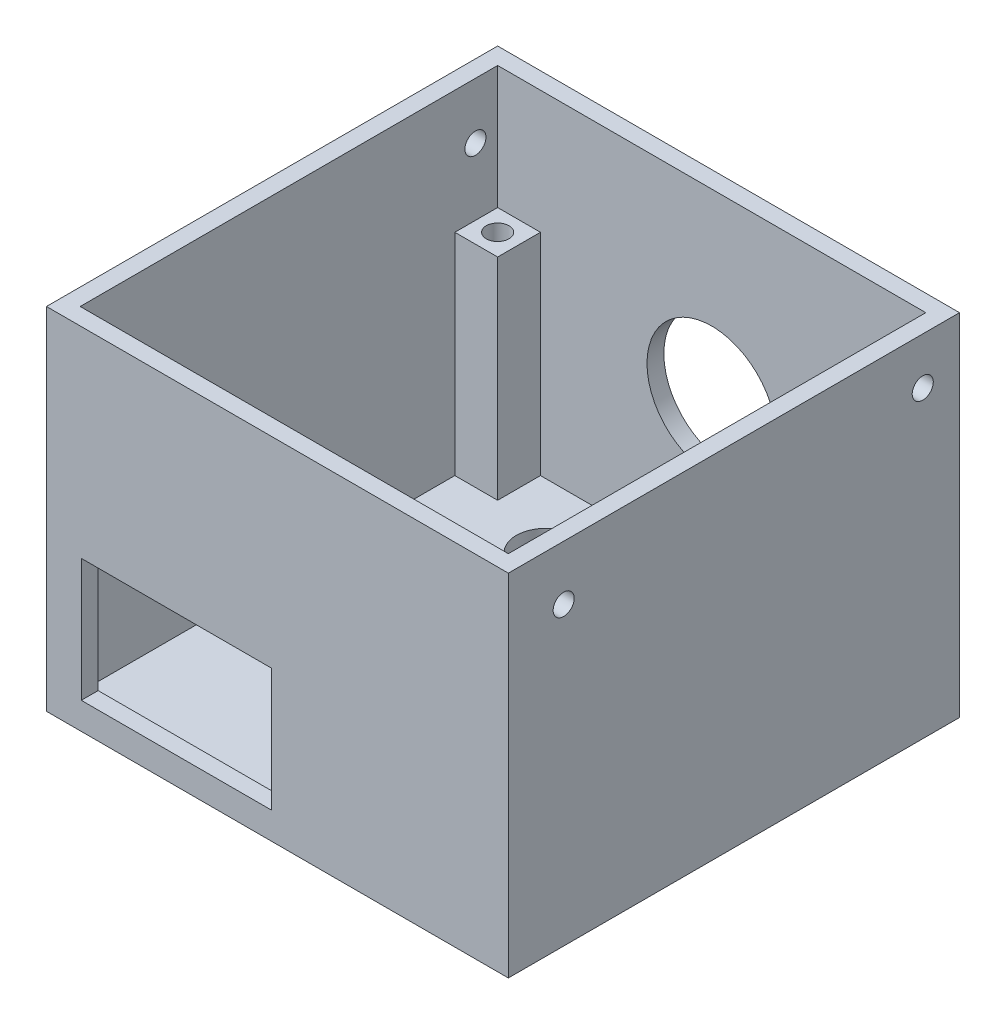
SolidWorks part; units mm, degrees
ref_plane "Front Plane" through (0, 0, 0) normal (0, 0, 1) x (1, 0, 0)
ref_plane "Top Plane" through (0, 0, 0) normal (0, 1, 0) x (1, 0, 0)
ref_plane "Right Plane" through (0, 0, 0) normal (1, 0, 0) x (0, 0, -1)
sketch "Sketch1" plane through (0, 0, 0) normal (0, 1, 0) x (1, 0, 0)
  line L1 (27.4, -26.765) -> (-27.4, -26.765)
  line L2 (27.4, -26.765) -> (27.4, 26.765)
  line L3 (27.4, 26.765) -> (-27.4, 26.765)
  line L4 (-27.4, -26.765) -> (-27.4, 26.765)
  line L5 (27.4, -26.765) -> (-27.4, 26.765) construction
  line L6 (27.4, 26.765) -> (-27.4, -26.765) construction
  point P0 (0, 0)
  dimension "D1" = 54.8
  dimension "D2" = 53.53
extrude "Boss-Extrude1" add sketch "Sketch1" along normal blind 41.6
sketch "Sketch2" plane through (0, 41.6, 0) normal (0, 1, 0) x (1, 0, 0)
  line L0 (-27.4, 26.765) -> (-27.4, -26.765) construction
  line L1 (25.4, -24.765) -> (-25.4, -24.765)
  line L2 (25.4, -24.765) -> (25.4, 24.765)
  line L3 (25.4, 24.765) -> (-25.4, 24.765)
  line L4 (-25.4, -24.765) -> (-25.4, 24.765)
  line L5 (25.4, -24.765) -> (-25.4, 24.765) construction
  line L6 (25.4, 24.765) -> (-25.4, -24.765) construction
  line L7 (27.4, 26.765) -> (-27.4, 26.765) construction
  point P0 (0, 0)
  dimension "D1" = 2
  dimension "D2" = 2
extrude "Cut-Extrude1" cut sketch "Sketch2" against normal blind 39.6
sketch "Sketch3" plane through (0, 2, 0) normal (0, 1, 0) x (1, 0, 0)
  line L1 (-25.4, 24.765) -> (-20.32, 24.765)
  line L2 (-25.4, 24.765) -> (-25.4, 19.685)
  line L3 (-25.4, 19.685) -> (-20.32, 19.685)
  line L4 (-20.32, 24.765) -> (-20.32, 19.685)
  line L5 (25.4, 24.765) -> (20.32, 24.765)
  line L6 (25.4, 24.765) -> (25.4, 19.685)
  line L7 (25.4, 19.685) -> (20.32, 19.685)
  line L8 (20.32, 24.765) -> (20.32, 19.685)
  line L9 (25.4, -24.765) -> (20.32, -24.765)
  line L10 (25.4, -24.765) -> (25.4, -19.685)
  line L11 (25.4, -19.685) -> (20.32, -19.685)
  line L12 (20.32, -24.765) -> (20.32, -19.685)
  dimension "D1" = 5.08
  dimension "D2" = 5.08
  dimension "D3" = 5.08
  dimension "D4" = 5.08
  dimension "D5" = 5.08
  dimension "D6" = 5.08
extrude "Boss-Extrude2" add sketch "Sketch3" along normal blind 25
sketch "Sketch4" plane through (0, 27, 0) normal (0, 1, 0) x (1, 0, 0)
  line L0 (-20.32, 19.685) -> (-20.32, 24.765) construction
  line L3 (-25.4, 19.685) -> (-20.32, 19.685) construction
  line L4 (20.32, 19.685) -> (25.4, 19.685) construction
  line L5 (20.32, 24.765) -> (20.32, 19.685) construction
  line L6 (25.4, -19.685) -> (20.32, -19.685) construction
  line L7 (20.32, -19.685) -> (20.32, -24.765) construction
  circle A0 centre (-22.86, 22.225) radius 1.35
  circle A1 centre (22.86, 22.225) radius 1.35
  circle A2 centre (22.86, -22.225) radius 1.35
  point P12 (22.86, -19.685)
  dimension "D1" = 2.54
  dimension "D3" = 2.54
  dimension "D5" = 2.54
  dimension "D2" = 2.54
  dimension "D4" = 2.54
  dimension "D6" = 2.54
extrude "Cut-Extrude2" cut sketch "Sketch4" against normal blind 10
sketch "Sketch5" plane through (0, 0, 0) normal (0, -1, 0) x (-1, 0, 0)
  circle A0 centre (-12.7629, 17.1869) radius 3.5
  circle A1 centre (12.1084, 17.1869) radius 3.5
extrude "Cut-Extrude3" cut sketch "Sketch5" against normal up to next
sketch "Sketch6" plane through (0, 0, 0) normal (0, -1, 0) x (-1, 0, 0)
  circle A0 centre (-16.9081, 1.5272) radius 3.1
  circle A1 centre (-8.7267, 1.5272) radius 3.1
extrude "Cut-Extrude4" cut sketch "Sketch6" against normal up to next
sketch "Sketch7" plane through (0, 0, 0) normal (0, -1, 0) x (-1, 0, 0)
  circle A0 centre (-12.6538, -10.0358) radius 3.6
extrude "Cut-Extrude5" cut sketch "Sketch7" against normal up to next
sketch "Sketch8" plane through (27.4, 0, 0) normal (1, 0, 0) x (0, 0, -1)
  circle A0 centre (-20.2009, 35.1133) radius 1.25
extrude "Cut-Extrude6" cut sketch "Sketch8" against normal up to next
sketch "Sketch10" plane through (-27.4, 0, 0) normal (-1, 0, 0) x (0, 0, 1)
  circle A0 centre (-22.1268, 34.9354) radius 1.25
extrude "Cut-Extrude7" cut sketch "Sketch10" against normal up to next
sketch "Sketch12" plane through (0, 0, -26.765) normal (0, 0, -1) x (-1, 0, 0)
  circle A0 centre (0, 19.8508) radius 7.6805
extrude "Cut-Extrude8" cut sketch "Sketch12" against normal up to next
sketch "Sketch13" plane through (0, 0, 26.765) normal (0, 0, 1) x (1, 0, 0)
  line L1 (-0.6897, 3.1964) -> (-23.2715, 3.1964)
  line L2 (-0.6897, 3.1964) -> (-0.6897, 17.7861)
  line L3 (-0.6897, 17.7861) -> (-23.2715, 17.7861)
  line L4 (-23.2715, 3.1964) -> (-23.2715, 17.7861)
  line L5 (-0.6897, 3.1964) -> (-23.2715, 17.7861) construction
  line L6 (-0.6897, 17.7861) -> (-23.2715, 3.1964) construction
  point P0 (-11.9806, 10.4912)
extrude "Cut-Extrude9" cut sketch "Sketch13" against normal up to next
sketch "Sketch14" plane through (27.4, 0, 0) normal (1, 0, 0) x (0, 0, -1)
  circle A0 centre (22.4032, 36.0407) radius 1.25
extrude "Cut-Extrude10" cut sketch "Sketch14" against normal up to next
